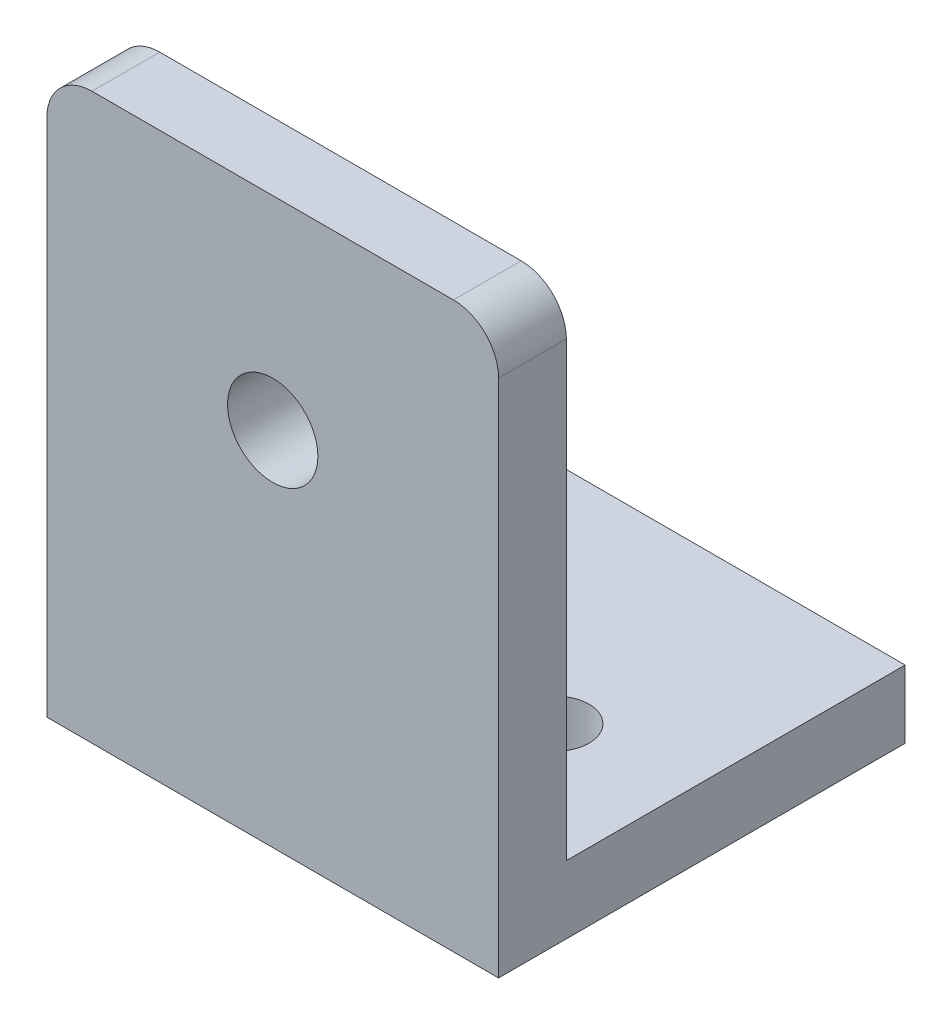
SolidWorks part; units mm, degrees
ref_plane "Front" through (0, 0, 0) normal (0, 0, 1) x (1, 0, 0)
ref_plane "Top" through (0, 0, 0) normal (0, 1, 0) x (1, 0, 0)
ref_plane "Right" through (0, 0, 0) normal (1, 0, 0) x (0, 0, -1)
sketch "草图1" plane through (0, 0, 0) normal (1, 0, 0) x (0, 0, -1)
  line L0 (0, 0) -> (0, 25)
  line L1 (0, 25) -> (3, 25)
  line L2 (3, 25) -> (3, 3)
  line L3 (3, 3) -> (18, 3)
  line L4 (18, 3) -> (18, 0)
  line L5 (18, 0) -> (0, 0)
  dimension "D1" = 25
  dimension "D2" = 3
  dimension "D3" = 22
  dimension "D4" = 15
extrude "凸台-拉伸1" add sketch "草图1" along normal blind 20
sketch "草图2" plane through (0, 3, 0) normal (0, 1, 0) x (1, 0, 0)
  line L0 (0, 8) -> (20, 8) construction
  line L1 (0, 18) -> (0, 3) construction
  line L2 (20, 18) -> (20, 3) construction
  line L3 (20, 0) -> (0, 0) construction
  circle A0 centre (5.5, 8) radius 1.5
  circle A1 centre (14.5, 8) radius 1.5
  dimension "D1" = 3
  dimension "D2" = 3
  dimension "D3" = 9
  dimension "D4" = 5.5
  dimension "D5" = 8
extrude "切除-拉伸1" cut sketch "草图2" against normal through all
fillet "圆角1" radius 2 2 edges at (0, 25, -1.5) (20, 25, -1.5)
sketch "草图3" plane through (0, 0, 0) normal (0, 0, 1) x (1, 0, 0)
  line L0 (10, 25) -> (10, 0) construction
  line L1 (18, 25) -> (2, 25) construction
  line L2 (20, 0) -> (0, 0) construction
  circle A0 centre (10, 16) radius 2
  dimension "D1" = 4
  dimension "D2" = 16
extrude "切除-拉伸2" cut sketch "草图3" against normal through all
